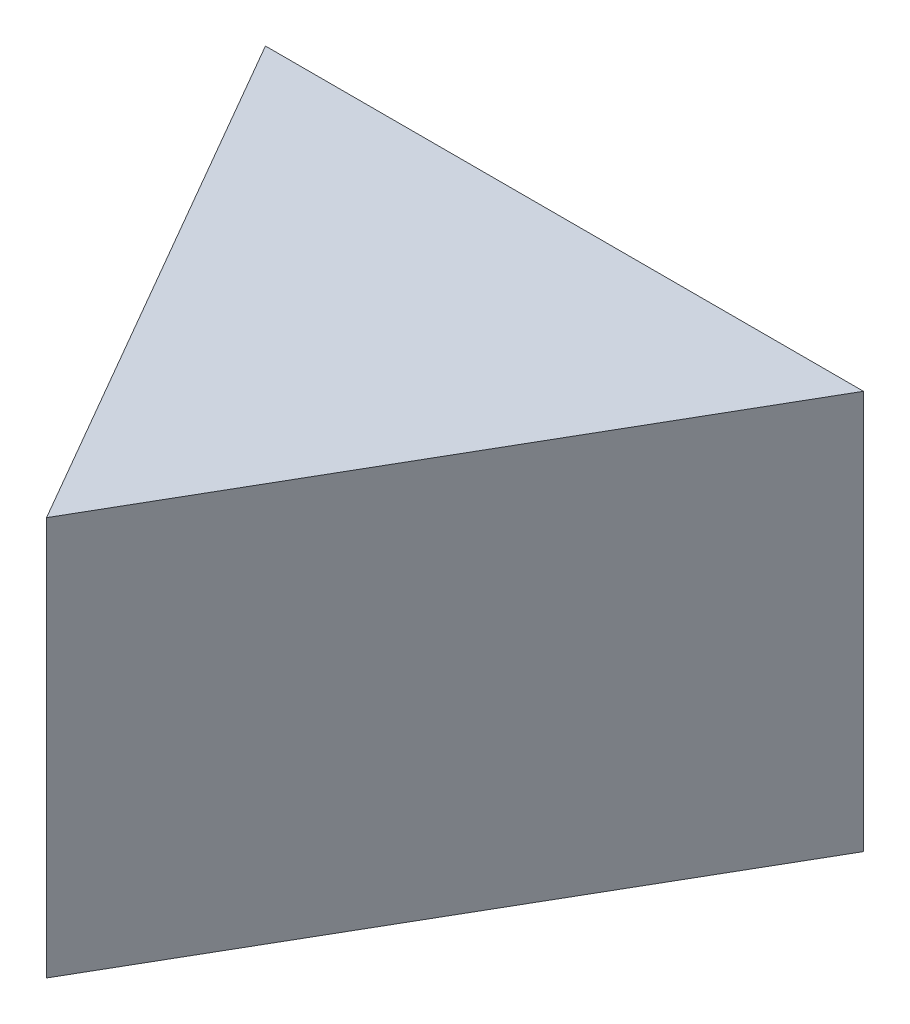
SolidWorks part; units mm, degrees
ref_plane "Front Plane" through (0, 0, 0) normal (0, 0, 1) x (1, 0, 0)
ref_plane "Top Plane" through (0, 0, 0) normal (0, 1, 0) x (1, 0, 0)
ref_plane "Right Plane" through (0, 0, 0) normal (1, 0, 0) x (0, 0, -1)
sketch "Sketch1" plane through (0, 0, 0) normal (0, 1, 0) x (1, 0, 0)
  line L1 (0, -43.9941) -> (38.1, 21.997)
  line L2 (38.1, 21.997) -> (-38.1, 21.997)
  line L3 (-38.1, 21.997) -> (0, -43.9941)
  circle A0 centre (0, 0) radius 21.997 construction
  dimension "D1" = 76.2
extrude "Boss-Extrude2" add sketch "Sketch1" along normal blind 25.4 and the other way blind 25.4
